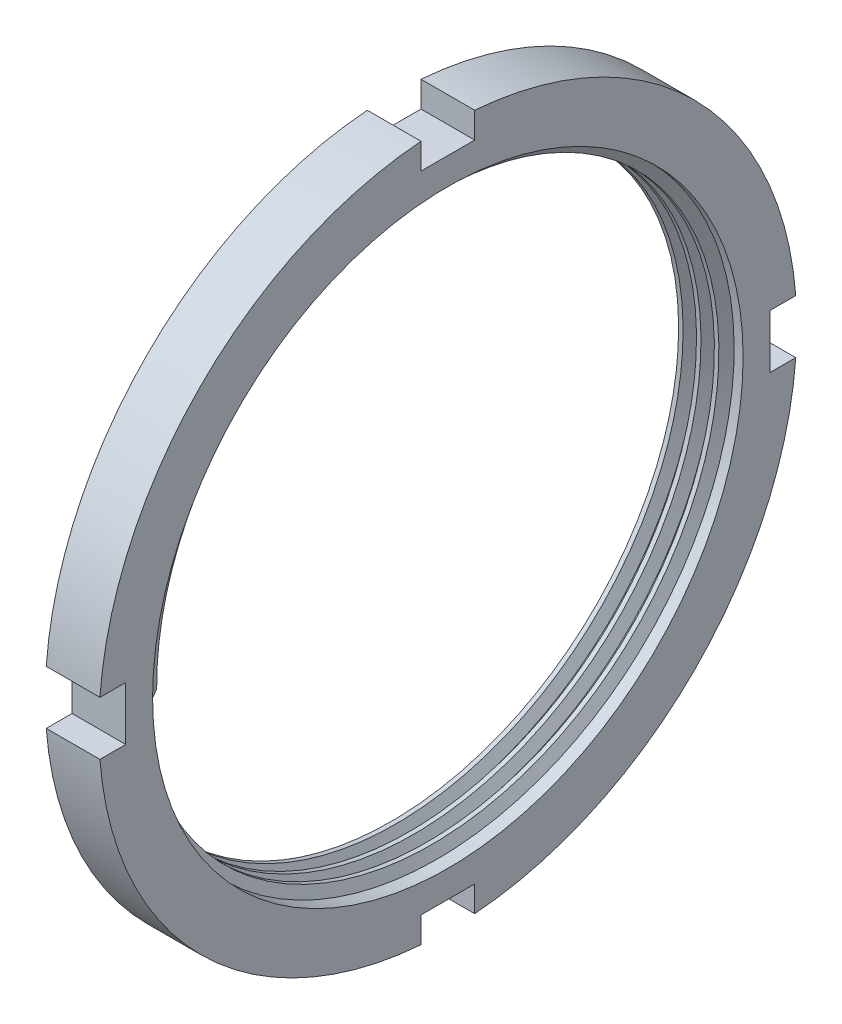
SolidWorks part; units mm, degrees
ref_plane "Front Plane" through (0, 0, 0) normal (0, 0, 1) x (1, 0, 0)
ref_plane "Top Plane" through (0, 0, 0) normal (0, 1, 0) x (1, 0, 0)
ref_plane "Right Plane" through (0, 0, 0) normal (1, 0, 0) x (0, 0, -1)
sketch "Sketch1" plane through (0, 0, 0) normal (1, 0, 0) x (0, 0, -1)
  circle A3 centre (0, 0) radius 20.6375
  circle A4 centre (0, 0) radius 17.4625
  dimension "D1" = 34.925
  dimension "D2" = 3.175
extrude "Boss-Extrude1" add sketch "Sketch1" along normal blind 3.175
thread "Thread1" pitch 1.0583 method extrude profile "Thread Profile1" start angle 0, offset 0, length 0, pitch 1.0583, diameter 34.925
ref_plane "Plane1" through (3.175, 0, 17.4625) normal (0, -1, 0) x (0, 0, 1)
sketch "Thread Profile1" plane through (3.175, 0, 17.4625) normal (0, -1, 0) x (0, 0, 1)
  line L0 (0, 0) -> (0, 1.0583) construction
  line L11 (0, 0) -> (0, 0.926)
  line L12 (0, 0.926) -> (-0.5728, 0.5953)
  line L13 (-0.5728, 0.5953) -> (-0.5728, 0.3307)
  line L15 (-0.5728, 0.3307) -> (0, 0)
  line L17 (-0.5728, 0.463) -> (0, 0.463) construction
  point P2 (0, 0)
  dimension "Pitch" = 1.0583
  dimension "Profile_Angle" = 60
  dimension "Profile_Land" = 0.2646
  dimension "Profile_Height" = 0.5728
sketch "Sketch4" plane through (3.175, 0, 0) normal (1, 0, 0) x (0, 0, -1)
  line L0 (-1.5875, 20.5764) -> (-1.5875, 19.05)
  line L1 (-1.5875, 19.05) -> (1.5875, 19.05)
  line L2 (1.5875, 19.05) -> (1.5875, 20.5764)
  line L3 (0, 19.05) -> (0, 20.6375) construction
  circle A0 centre (0, 0) radius 20.6375 construction
  dimension "D1" = 1.5875
  dimension "D2" = 3.175
extrude "Cut-Extrude1" cut sketch "Sketch4" against normal through all and the other way through all
sketch "Sketch5" plane through (0, 0, 0) normal (0, 1, 0) x (1, 0, 0)
  line L0 (-17.5467, 0) -> (16.7774, 0) construction
pattern_circular "CirPattern1" count 4 over 360 about axis through (-17.5467, 0, 0) along (1, 0, 0) of "Cut-Extrude1"
